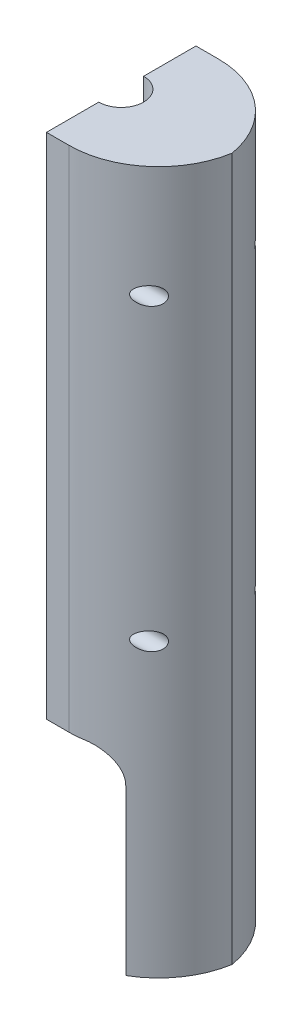
SolidWorks part; units mm, degrees
ref_plane "Plan de face" through (0, 0, 0) normal (0, 0, 1) x (1, 0, 0)
ref_plane "Plan de dessus" through (0, 0, 0) normal (0, 1, 0) x (1, 0, 0)
ref_plane "Plan de droite" through (0, 0, 0) normal (1, 0, 0) x (0, 0, -1)
sketch "Esquisse1" plane through (0, 0, 0) normal (0, 0, 1) x (1, 0, 0)
  line L0 (-129.3911, 131.107) -> (-129.3911, -98.893)
  line L1 (-129.3911, -98.893) -> (-124.3911, -98.893)
  line L2 (-124.3911, -98.893) -> (-124.3911, -33.893)
  line L3 (-124.3911, -33.893) -> (-64.3911, -33.893)
  line L4 (-64.3911, -33.893) -> (-64.3911, -98.893)
  line L5 (-64.3911, -98.893) -> (-49.3911, -98.893)
  line L6 (-49.3911, -98.893) -> (-49.3911, 131.107)
  line L7 (-49.3911, 131.107) -> (-129.3911, 131.107)
  dimension "D1" = 230
  dimension "D2" = 80
  dimension "D3" = 60
  dimension "D4" = 15
extrude "Boss.-Extru.1" add sketch "Esquisse1" along normal blind 50
fillet "Congé4" radius 35 1 edges at (-129.3911, 16.107, 50)
fillet "Congé5" radius 35 1 edges at (-129.3911, 16.107, 0)
fillet "Congé6" radius 30 2 edges at (-49.3911, 16.107, 0) (-49.3911, 16.107, 50)
fillet "Congé12" radius 10 2 edges at (-124.3911, -33.893, 21.147) (-64.3911, -33.893, 25)
sketch "Esquisse5" plane through (0, 131.107, 0) normal (0, 1, 0) x (1, 0, 0)
  line L0 (-86.8911, -50) -> (-86.8911, 0)
  line L1 (-79.3911, -50) -> (-94.3911, -50) construction
  arc A0 (-86.8911, -50) -> (-86.8911, 0) centre (-120.3634, -25) cw
extrude "Enlèv. mat.-Extru.8" cut sketch "Esquisse5" against normal blind 251
sketch "Esquisse6" plane through (-86.8911, 0, 0) normal (-1, 0, 0) x (0, 0, 1)
  line L0 (25, 131.107) -> (25, -33.893) construction
  line L1 (50, 131.107) -> (0, 131.107) construction
  line L2 (50, -33.893) -> (0, -33.893) construction
  line L4 (50, -33.893) -> (50, 131.107) construction
  line L5 (50, 48.607) -> (0, 48.607) construction
  line L6 (0, -33.893) -> (0, 131.107) construction
  circle A0 centre (7.5, 98.607) radius 2
  circle A1 centre (42.5, 98.607) radius 2
  circle A2 centre (42.5, -1.393) radius 2
  circle A3 centre (7.5, -1.393) radius 2
  dimension "D1" = 35
  dimension "D2" = 50
extrude "Enlèv. mat.-Extru.9" cut sketch "Esquisse6" against normal blind 58
sketch "Esquisse9" plane through (0, 131.107, 0) normal (0, 1, 0) x (1, 0, 0)
  line L0 (-86.8911, -50) -> (-86.8911, 0) construction
  line L1 (-49.8107, -25) -> (-86.8911, -25) construction
  arc A0 (-86.8911, -17.5) -> (-86.8911, -32.5) centre (-86.8911, -25) cw
  point P8 (-94.3911, -25)
  dimension "D1" = 15
extrude "Enlèv. mat.-Extru.12" cut sketch "Esquisse9" against normal blind 179 and the other way through all flip side to cut
ref_plane "Plan2" through (-49.8107, 0, 0) normal (-1, 0, 0) x (0, 0, 1)
sketch "Esquisse11" plane through (-49.8107, 0, 0) normal (-1, 0, 0) x (0, 0, 1)
  circle A8 centre (42.5, 98.607) radius 3
  circle A9 centre (7.5, 98.607) radius 3
  circle A10 centre (42.5, -1.393) radius 3
  circle A11 centre (7.5, -1.393) radius 3
extrude "Enlèv. mat.-Extru.14" cut sketch "Esquisse11" along normal blind 20
sketch "Esquisse12" plane through (0, 131.107, 0) normal (0, 1, 0) x (1, 0, 0)
  line L0 (-79.3911, 0) -> (-86.8911, 0) construction
  line L1 (-86.8911, -17.5) -> (-86.8911, 0) construction
  line L2 (-86.8911, -50) -> (-86.8911, -32.5) construction
  line L3 (-79.3911, -50) -> (-86.8911, -50) construction
  line L4 (-79.3911, 0) -> (-86.8911, 0)
  line L5 (-86.8911, -17.5) -> (-86.8911, 0)
  line L6 (-86.8911, -50) -> (-86.8911, -32.5)
  line L7 (-79.3911, -50) -> (-86.8911, -50)
  arc A0 (-86.8911, -32.5) -> (-86.8911, -17.5) centre (-86.8911, -25) ccw construction
  arc A1 (-79.3911, -50) -> (-49.8107, -25) centre (-79.3911, -20) ccw construction
  arc A2 (-49.8107, -25) -> (-79.3911, 0) centre (-79.3911, -30) ccw construction
  arc A3 (-86.8911, -32.5) -> (-86.8911, -17.5) centre (-86.8911, -25) ccw
  arc A4 (-79.3911, -50) -> (-49.8107, -25) centre (-79.3911, -20) ccw
  arc A5 (-49.8107, -25) -> (-79.3911, 0) centre (-79.3911, -30) ccw
extrude "Boss.-Extru.2" add sketch "Esquisse12" along normal blind 5
sketch "Esquisse13" plane through (-64.3911, 0, 0) normal (-1, 0, 0) x (0, 0, 1)
  line L0 (25, -43.893) -> (25, -98.893) construction
  line L1 (45.9808, -43.893) -> (4.0192, -43.893) construction
  line L2 (45.9808, -98.893) -> (4.0192, -98.893) construction
  line L4 (45.9808, -98.893) -> (45.9808, -43.893) construction
  line L5 (45.9808, -71.393) -> (4.0192, -71.393) construction
  line L6 (4.0192, -43.893) -> (4.0192, -98.893) construction
  line L7 (21, -56.393) -> (29, -56.393)
  line L8 (21, -56.393) -> (21, -86.393)
  line L9 (21, -86.393) -> (29, -86.393)
  line L10 (29, -56.393) -> (29, -86.393)
  line L11 (21, -56.393) -> (29, -86.393) construction
  line L12 (21, -86.393) -> (29, -56.393) construction
  line L13 (10, -67.393) -> (40, -67.393)
  line L14 (10, -67.393) -> (10, -75.393)
  line L15 (10, -75.393) -> (40, -75.393)
  line L16 (40, -67.393) -> (40, -75.393)
  line L17 (10, -67.393) -> (40, -75.393) construction
  line L18 (10, -75.393) -> (40, -67.393) construction
  point P12 (25, -71.393)
  point P17 (25, -71.393)
extrude "Enlèv. mat.-Extru.15" cut sketch "Esquisse13" against normal blind 4 contours L16 L13 L10 L15 | L14 L15 L8 L13 | L8 L15 L10 L13 | L7 L10 L9 L8 region at (-64.3911, -71.393, 25) region at (-64.3911, -71.393, 15.5) region at (-64.3911, -71.393, 34.5)
